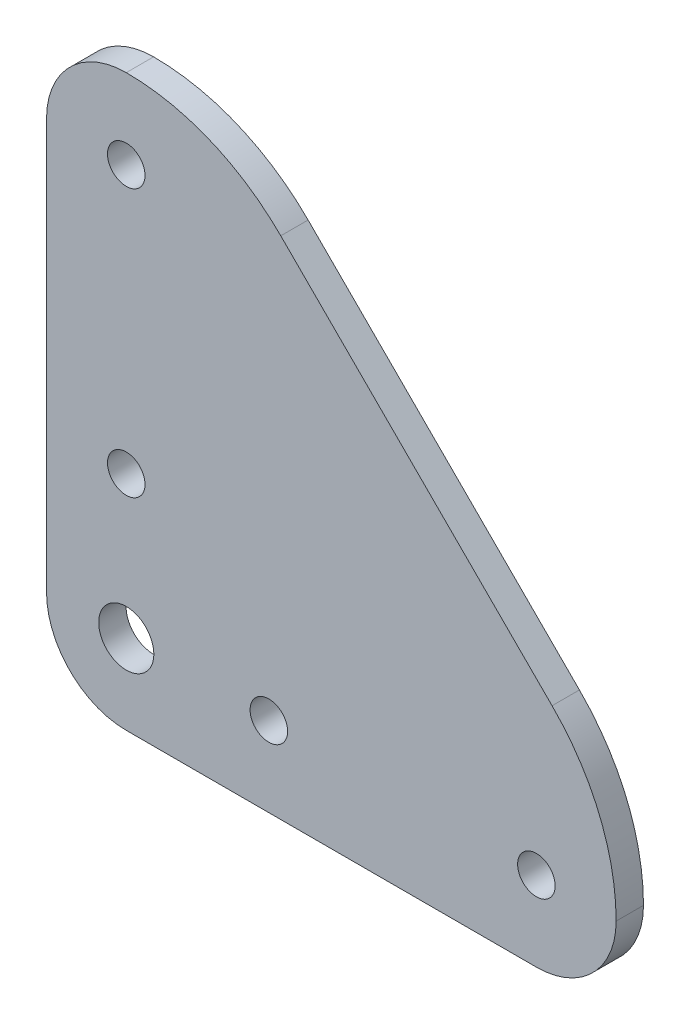
SolidWorks part; units mm, degrees
material "PET"
ref_plane "Front Plane" through (0, 0, 0) normal (0, 0, 1) x (1, 0, 0)
ref_plane "Top Plane" through (0, 0, 0) normal (0, 1, 0) x (1, 0, 0)
ref_plane "Right Plane" through (0, 0, 0) normal (1, 0, 0) x (0, 0, -1)
sketch "Sketch1" plane through (0, 0, 0) normal (0, 0, 1) x (1, 0, 0)
  line L0 (0, 0) -> (0, 133)
  line L1 (21.5, 21.5) -> (66.5, 21.5) construction
  line L2 (66.5, 21.5) -> (111.5, 21.5) construction
  line L3 (21.5, 21.5) -> (21.5, 52.7884) construction
  line L4 (43, 133) -> (0, 133)
  line L5 (133, 0) -> (0, 0)
  line L6 (21.5, 52.7884) -> (21.5, 84.0768) construction
  line L7 (133, 43) -> (133, 0)
  line L8 (43, 133) -> (133, 43)
  line L9 (133, 21.5) -> (111.5, 21.5) construction
  line L10 (21.5, 133) -> (21.5, 84.0768) construction
  circle A0 centre (21.5, 21.5) radius 6.05
  circle A1 centre (21.5, 111.5) radius 4.1187
  circle A2 centre (111.5, 21.5) radius 4.1188
  circle A3 centre (21.5, 52.7884) radius 4.1188
  circle A4 centre (52.7884, 21.5) radius 4.1188
  dimension "D1" = 90
  dimension "E" = 12.1
  dimension "D2" = 21.5
  dimension "D6" = 8.2375
  dimension "C" = 133
  dimension "D3" = 31.2884
  dimension "B" = 133
  dimension "D4" = 21.5
  dimension "D5" = 21.5
  dimension "D7" = 31.2884
extrude "Boss-Extrude1" add sketch "Sketch1" along normal mid plane 6
fillet "Fillet1" radius 21.5 3 edges at (0, 0, 0) (133, 0, 0) (0, 133, 0)
fillet "Fillet2" radius 52 2 edges at (133, 43, 0) (43, 133, 0)
sketch "Sketch2" plane through (0, 0, 3) normal (0, 0, 1) x (1, 0, 0)
  line L6 (114.9411, 55.402) -> (55.402, 114.9411)
  line L7 (4, 111.5) -> (4, 21.5)
  line L8 (21.5, 4) -> (111.5, 4)
  line L9 (114.9411, 55.402) -> (55.402, 114.9411)
  line L10 (4, 111.5) -> (4, 21.5)
  line L11 (21.5, 4) -> (111.5, 4)
  line L12 (117.7696, 58.2304) -> (58.2304, 117.7696)
  line L13 (0, 111.5) -> (0, 21.5)
  line L14 (21.5, 0) -> (111.5, 0)
  line L15 (117.7696, 58.2304) -> (58.2304, 117.7696)
  line L16 (0, 111.5) -> (0, 21.5)
  line L17 (21.5, 0) -> (111.5, 0)
  arc A10 (111.5, 4) -> (129, 21.4985) centre (111.5, 21.5) ccw
  arc A11 (129, 21.4985) -> (114.9411, 55.402) centre (81, 21.4609) ccw
  arc A12 (55.402, 114.9411) -> (21.4985, 129) centre (21.4609, 81) ccw
  arc A13 (21.4985, 129) -> (4, 111.5) centre (21.5, 111.5) ccw
  arc A14 (4, 21.5) -> (21.5, 4) centre (21.5, 21.5) ccw
  arc A15 (111.5, 4) -> (129, 21.4985) centre (111.5, 21.5) ccw
  arc A16 (129, 21.4985) -> (114.9411, 55.402) centre (81, 21.4609) ccw
  arc A17 (55.402, 114.9411) -> (21.4985, 129) centre (21.4609, 81) ccw
  arc A18 (21.4985, 129) -> (4, 111.5) centre (21.5, 111.5) ccw
  arc A19 (4, 21.5) -> (21.5, 4) centre (21.5, 21.5) ccw
  arc A20 (111.5, 0) -> (133, 21.5) centre (111.5, 21.5) ccw
  arc A21 (133, 21.5) -> (117.7696, 58.2304) centre (81, 21.4609) ccw
  arc A22 (58.2304, 117.7696) -> (21.5, 133) centre (21.4609, 81) ccw
  arc A23 (21.5, 133) -> (0, 111.5) centre (21.5, 111.5) ccw
  arc A24 (0, 21.5) -> (21.5, 0) centre (21.5, 21.5) ccw
  arc A25 (111.5, 0) -> (133, 21.5) centre (111.5, 21.5) ccw
  arc A26 (133, 21.5) -> (117.7696, 58.2304) centre (81, 21.4609) ccw
  arc A27 (58.2304, 117.7696) -> (21.5, 133) centre (21.4609, 81) ccw
  arc A28 (21.5, 133) -> (0, 111.5) centre (21.5, 111.5) ccw
  arc A29 (0, 21.5) -> (21.5, 0) centre (21.5, 21.5) ccw
  dimension "D1" = 4
  dimension "D2" = 0
extrude "Cut-Extrude1" cut sketch "Sketch2" against normal through all body kept at (129, 21.4985, -3)
